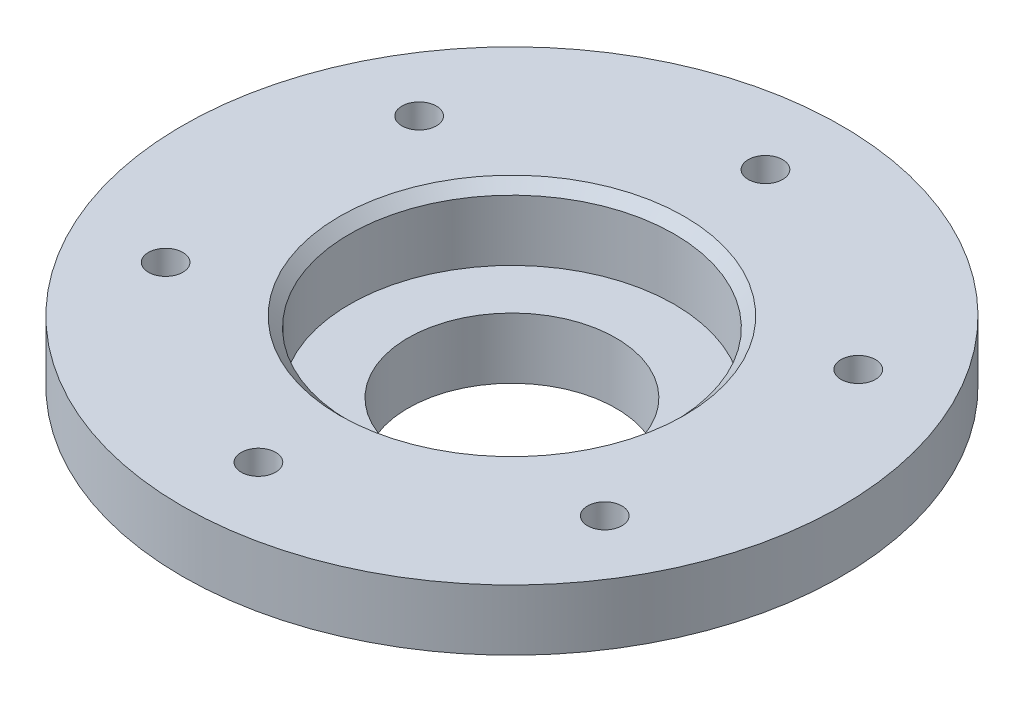
SolidWorks part; units mm, degrees
ref_plane "Ebene vorne" through (0, 0, 0) normal (0, 0, 1) x (1, 0, 0)
ref_plane "Ebene oben" through (0, 0, 0) normal (0, 1, 0) x (1, 0, 0)
ref_plane "Ebene rechts" through (0, 0, 0) normal (1, 0, 0) x (0, 0, -1)
sketch "Skizze1" plane through (0, 0, 0) normal (0, 0, 1) x (1, 0, 0)
  line L0 (0, 0) -> (0, -16486.4459) construction
  line L1 (10.25, 0) -> (20, 0)
  line L2 (20, 0) -> (20, 7)
  line L3 (20, 7) -> (32.5, 7)
  line L4 (32.5, 7) -> (32.5, 13)
  line L5 (32.5, 13) -> (16, 13)
  line L6 (16, 13) -> (16, 6)
  line L7 (16, 6) -> (10.25, 6)
  line L8 (10.25, 6) -> (10.25, 0)
  dimension "D1" = 40
  dimension "D2" = 65
  dimension "D3" = 13
  dimension "D4" = 20.5
  dimension "D5" = 32
  dimension "D6" = 7
  dimension "D7" = 7
revolve "Rotation1" add sketch "Skizze1" angle 360 about L0
chamfer "Fase1" distance 1 angle 45 1 edges at (0, 13, 16)
chamfer "Fase2" distance 1 angle 45 1 edges at (0, 0, 20)
hole_wizard "Formsenkung für M3 Senkschraube mit Schlitz/Kreuzschlitz1" positions "Skizze2" profile "Skizze3" countersink size "M3" standard "ISO" end condition through all
sketch "Skizze2" plane through (0, 7, 0) normal (0, -1, 0) x (-1, 0, 0)
  line L0 (0, 0) -> (0, -50000) construction
  point P5 (0, 25)
  dimension "D1" = 25
sketch "Skizze3" plane through (0, 7, -25) normal (1, 0, 0) x (0, 0, -1)
  line L0 (0, 0) -> (0, 6)
  line L1 (0, 6) -> (1.7, 6)
  line L2 (1.7, 6) -> (1.7, 1.45)
  line L3 (1.7, 1.45) -> (3.15, 0)
  line L5 (3.15, 0) -> (0, 0)
  line L6 (-1.7, 1.45) -> (-3.15, 0) construction
  line L11 (0, -6.35) -> (0, 107.95) construction
  dimension "Bohrerdurchmesser" = 3.4
  dimension "Bohrungstiefe" = 6
  dimension "Senkdurchmesser (Oben)" = 6.3
  dimension "Senkwinkel (Oben)" = 90
pattern_circular "Kreismuster1" count 6 over 360 about axis through (0, 0, 0) along (0, -1, 0) of "Formsenkung für M3 Senkschraube mit Schlitz/Kreuzschlitz1"
